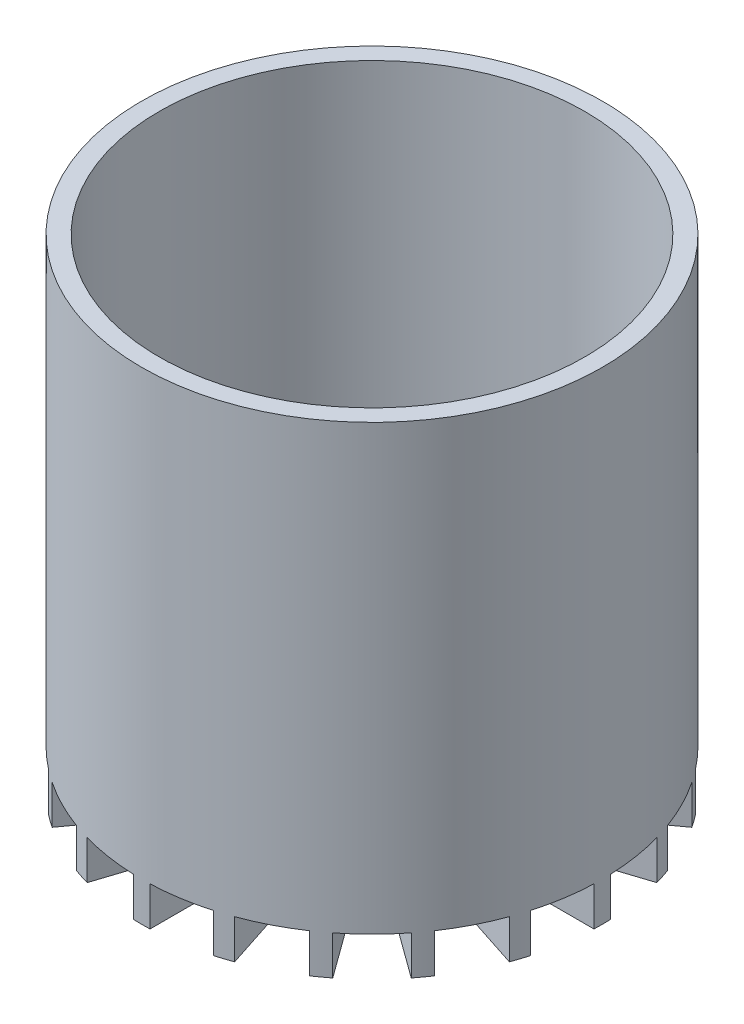
SolidWorks part; units mm, degrees
ref_plane "Front Plane" through (0, 0, 0) normal (0, 0, 1) x (1, 0, 0)
ref_plane "Top Plane" through (0, 0, 0) normal (0, 1, 0) x (1, 0, 0)
ref_plane "Right Plane" through (0, 0, 0) normal (1, 0, 0) x (0, 0, -1)
sketch "Sketch1" plane through (0, 0, 0) normal (0, 1, 0) x (1, 0, 0)
  circle A0 centre (0, 0) radius 38.1
  dimension "D1" = 76.2
extrude "Boss-Extrude1" add sketch "Sketch1" along normal blind 76.2
shell "Shell2" thickness 3.175 removed face at (0, 76.2, 38.1) outward yes
ref_axis "Axis1" through (0, 76.2, 0) along (0, -1, 0)
sketch "Sketch2" plane through (0, -3.175, 0) normal (0, -1, 0) x (-1, 0, 0)
  line L0 (0, 0) -> (0, 41.275)
  line L1 (-1.5, -41.275) -> (-1.5, 41.275)
  line L2 (-1.5, -41.275) -> (1.5, -41.275)
  line L3 (-1.5, 41.275) -> (1.5, 41.275)
  line L4 (1.5, -41.275) -> (1.5, 41.275)
  line L5 (-1.5, -41.275) -> (1.5, 41.275) construction
  line L6 (-1.5, 41.275) -> (1.5, -41.275) construction
  line L7 (-23.0473, -34.2739) -> (25.4744, 32.5105)
  line L8 (-25.4744, -32.5105) -> (23.0473, 34.2739)
  line L9 (-25.4744, -32.5105) -> (-23.0473, -34.2739)
  line L10 (23.0473, 34.2739) -> (25.4744, 32.5105)
  line L11 (-38.7913, -14.1813) -> (39.7184, 11.3281)
  line L12 (-39.7184, -11.3281) -> (38.7913, 14.1813)
  line L13 (-39.7184, -11.3281) -> (-38.7913, -14.1813)
  line L14 (38.7913, 14.1813) -> (39.7184, 11.3281)
  line L15 (-39.7184, 11.3281) -> (38.7913, -14.1813)
  line L16 (-38.7913, 14.1813) -> (39.7184, -11.3281)
  line L17 (-38.7913, 14.1813) -> (-39.7184, 11.3281)
  line L18 (39.7184, -11.3281) -> (38.7913, -14.1813)
  line L19 (-25.4744, 32.5105) -> (23.0473, -34.2739)
  line L20 (-23.0473, 34.2739) -> (25.4744, -32.5105)
  line L21 (-23.0473, 34.2739) -> (-25.4744, 32.5105)
  line L22 (25.4744, -32.5105) -> (23.0473, -34.2739)
  line L23 (-1.5, 41.275) -> (-1.5, -41.275)
  line L24 (1.5, 41.275) -> (1.5, -41.275)
  line L25 (1.5, 41.275) -> (-1.5, 41.275)
  line L26 (1.5, -41.275) -> (-1.5, -41.275)
  line L27 (-14.1813, 38.7913) -> (11.3281, -39.7184)
  line L28 (14.1813, -38.7913) -> (11.3281, -39.7184)
  line L29 (-11.3281, 39.7184) -> (14.1813, -38.7913)
  line L30 (-11.3281, 39.7184) -> (-14.1813, 38.7913)
  line L31 (11.3281, 39.7184) -> (-14.1813, -38.7913)
  line L32 (-11.3281, -39.7184) -> (-14.1813, -38.7913)
  line L33 (14.1813, 38.7913) -> (-11.3281, -39.7184)
  line L34 (14.1813, 38.7913) -> (11.3281, 39.7184)
  line L35 (32.5105, 25.4744) -> (-34.2739, -23.0473)
  line L36 (-32.5105, -25.4744) -> (-34.2739, -23.0473)
  line L37 (34.2739, 23.0473) -> (-32.5105, -25.4744)
  line L38 (34.2739, 23.0473) -> (32.5105, 25.4744)
  line L39 (-41.275, 1.5) -> (41.275, 1.5)
  line L40 (-41.275, 1.5) -> (-41.275, -1.5)
  line L41 (-41.275, -1.5) -> (41.275, -1.5)
  line L42 (41.275, 1.5) -> (41.275, -1.5)
  line L43 (-34.2739, 23.0473) -> (32.5105, -25.4744)
  line L44 (34.2739, -23.0473) -> (32.5105, -25.4744)
  line L45 (-32.5105, 25.4744) -> (34.2739, -23.0473)
  line L46 (-32.5105, 25.4744) -> (-34.2739, 23.0473)
  line L47 (38.7913, 14.1813) -> (-39.7184, -11.3281)
  line L48 (-38.7913, -14.1813) -> (-39.7184, -11.3281)
  line L49 (39.7184, 11.3281) -> (-38.7913, -14.1813)
  line L50 (39.7184, 11.3281) -> (38.7913, 14.1813)
  line L51 (39.7184, -11.3281) -> (-38.7913, 14.1813)
  line L52 (-39.7184, 11.3281) -> (-38.7913, 14.1813)
  line L53 (38.7913, -14.1813) -> (-39.7184, 11.3281)
  line L54 (38.7913, -14.1813) -> (39.7184, -11.3281)
  line L55 (25.4744, -32.5105) -> (-23.0473, 34.2739)
  line L56 (-25.4744, 32.5105) -> (-23.0473, 34.2739)
  line L57 (23.0473, -34.2739) -> (-25.4744, 32.5105)
  line L58 (23.0473, -34.2739) -> (25.4744, -32.5105)
  line L59 (1.5, 41.275) -> (1.5, -41.275)
  line L60 (1.5, 41.275) -> (-1.5, 41.275)
  line L61 (-1.5, 41.275) -> (-1.5, -41.275)
  line L62 (1.5, -41.275) -> (-1.5, -41.275)
  line L63 (23.0473, 34.2739) -> (-25.4744, -32.5105)
  line L64 (-23.0473, -34.2739) -> (-25.4744, -32.5105)
  line L65 (25.4744, 32.5105) -> (-23.0473, -34.2739)
  line L66 (25.4744, 32.5105) -> (23.0473, 34.2739)
  line L67 (14.1813, -38.7913) -> (-11.3281, 39.7184)
  line L68 (-14.1813, 38.7913) -> (-11.3281, 39.7184)
  line L69 (11.3281, -39.7184) -> (-14.1813, 38.7913)
  line L70 (11.3281, -39.7184) -> (14.1813, -38.7913)
  line L71 (-11.3281, -39.7184) -> (14.1813, 38.7913)
  line L72 (11.3281, 39.7184) -> (14.1813, 38.7913)
  line L73 (-14.1813, -38.7913) -> (11.3281, 39.7184)
  line L74 (-14.1813, -38.7913) -> (-11.3281, -39.7184)
  line L75 (-32.5105, -25.4744) -> (34.2739, 23.0473)
  line L76 (32.5105, 25.4744) -> (34.2739, 23.0473)
  line L77 (-34.2739, -23.0473) -> (32.5105, 25.4744)
  line L78 (-34.2739, -23.0473) -> (-32.5105, -25.4744)
  line L79 (41.275, -1.5) -> (-41.275, -1.5)
  line L80 (41.275, -1.5) -> (41.275, 1.5)
  line L81 (41.275, 1.5) -> (-41.275, 1.5)
  line L82 (-41.275, -1.5) -> (-41.275, 1.5)
  line L83 (34.2739, -23.0473) -> (-32.5105, 25.4744)
  line L84 (-34.2739, 23.0473) -> (-32.5105, 25.4744)
  line L85 (32.5105, -25.4744) -> (-34.2739, 23.0473)
  line L86 (32.5105, -25.4744) -> (34.2739, -23.0473)
  circle A1 centre (0, 0) radius 41.275 construction
  circle A2 centre (0, 0) radius 41.275
  dimension "D1" = 3
  dimension "D2" = 6
  dimension "D3" = 4
extrude "Boss-Extrude2" add sketch "Sketch2" along normal blind 7 contours L4 L3 L1 L2 | L7 L10 L8 L9 | L11 L14 L12 L13 | L15 L18 L16 L17 | L20 L22 L19 L21 | L35 L36 L37 L38 | L39 L42 L41 L40 | L43 L44 L45 L46 | L27 L28 L29 L30 | L31 L32 L33 L34
sketch "Sketch3" plane through (0, -3.175, 0) normal (0, -1, 0) x (1, 0, 0)
  circle A0 centre (0, 0) radius 41.275
  circle A1 centre (0, 0) radius 61.9063
extrude "Cut-Extrude1" cut sketch "Sketch3" against normal through all both and the other way through all
sketch "Sketch4" plane through (0, -10.175, 0) normal (0, -1, 0) x (1, 0, 0)
  circle A0 centre (0, 0) radius 20.64
extrude "Cut-Extrude2" cut sketch "Sketch4" against normal up to surface (7 mm away) up to face at (30.2359, -3.175, -4.7889)
scale "Scale1" scale about centroid uniform scaling yes scale factor 0.615385
